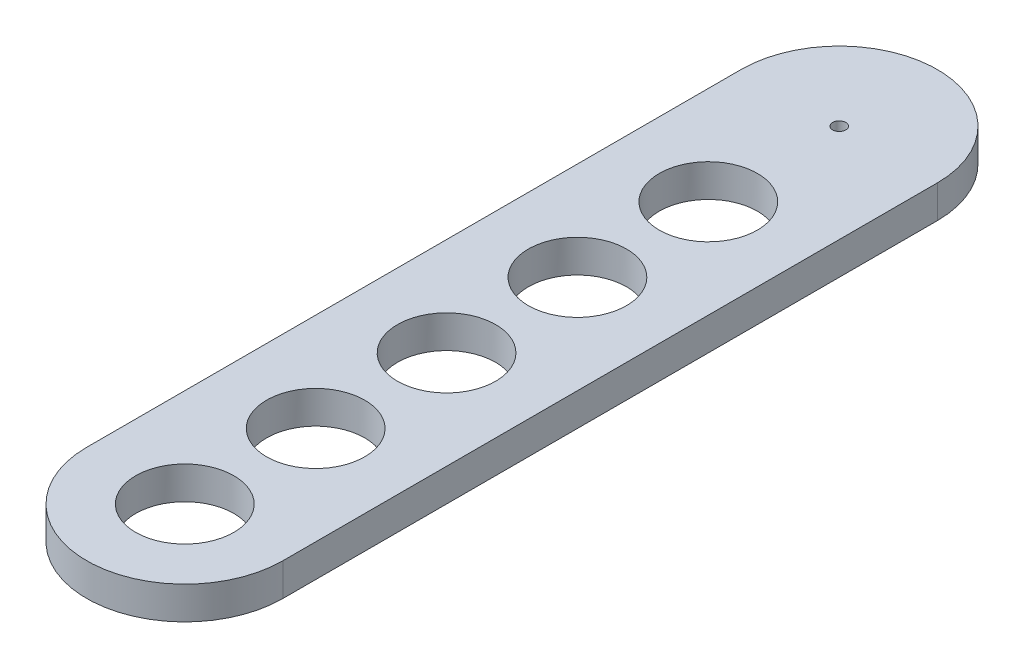
SolidWorks part; units mm, degrees
ref_plane "Front Plane" through (0, 0, 0) normal (0, 0, 1) x (1, 0, 0)
ref_plane "Top Plane" through (0, 0, 0) normal (0, 1, 0) x (1, 0, 0)
ref_plane "Right Plane" through (0, 0, 0) normal (1, 0, 0) x (0, 0, -1)
sketch "Sketch1" plane through (0, 0, 0) normal (0, 1, 0) x (1, 0, 0)
  line L1 (0, 0) -> (30, 0)
  line L2 (0, 0) -> (0, 130)
  line L3 (0, 130) -> (30, 130)
  line L4 (30, 0) -> (30, 130)
  dimension "D1" = 130
  dimension "D2" = 30
extrude "Boss-Extrude1" add sketch "Sketch1" along normal blind 5
ref_plane "Plane1" through (15, 0, 0) normal (-1, 0, 0) x (0, 0, 1)
sketch "Sketch2" plane through (0, 5, 0) normal (0, 1, 0) x (1, 0, 0)
  line L0 (0, 15) -> (30, 15) construction
  line L1 (0, 130) -> (0, 0) construction
  line L2 (30, 0) -> (30, 130) construction
  line L3 (0, 0) -> (30, 0) construction
  circle A0 centre (15, 15) radius 7.5
  dimension "D1" = 15
  dimension "D2" = 15
extrude "Cut-Extrude1" cut sketch "Sketch2" against normal up to next
pattern_linear "LPattern1" count 5 spacing 20 along (0, 0, -1) of "Cut-Extrude1"
fillet "Fillet1" 2 edges at (0, 2.5, 0) (30, 2.5, 0) type full round first side face at (0, 2.5, -65) second side face at (30, 2.5, -65) middle face at (15, 2.5, 0)
fillet "Fillet2" 2 edges at (30, 2.5, -130) (0, 2.5, -130) type full round first side face at (30, 2.5, -72.5) second side face at (0, 2.5, -72.5) middle face at (15, 2.5, -130)
hole_wizard "Ø2.0mm Dowel Hole1" positions "Sketch3" profile "Sketch4" hole size "Ø2.0" standard "ANSI Metric" end condition up to next
sketch "Sketch3" plane through (0, 5, 0) normal (0, 1, 0) x (1, 0, 0)
  line L0 (15, 2.75) -> (15, -2.75) construction
  arc A0 (30, 115) -> (0, 115) centre (15, 115) ccw construction
  point P0 (15, 115)
  point P10 (15, 130)
  dimension "D1" = 15
sketch "Sketch4" plane through (15, 5, -115) normal (1, 0, 0) x (0, 0, 1)
  line L0 (0, 0) -> (0, 5)
  line L1 (0, 5) -> (1, 5)
  line L2 (1, 5) -> (1, 0)
  line L5 (1, 0) -> (0, 0)
  line L11 (0, -6.35) -> (0, 107.95) construction
  dimension "Thru Hole Dia." = 2
  dimension "Thru Hole Depth" = 5
